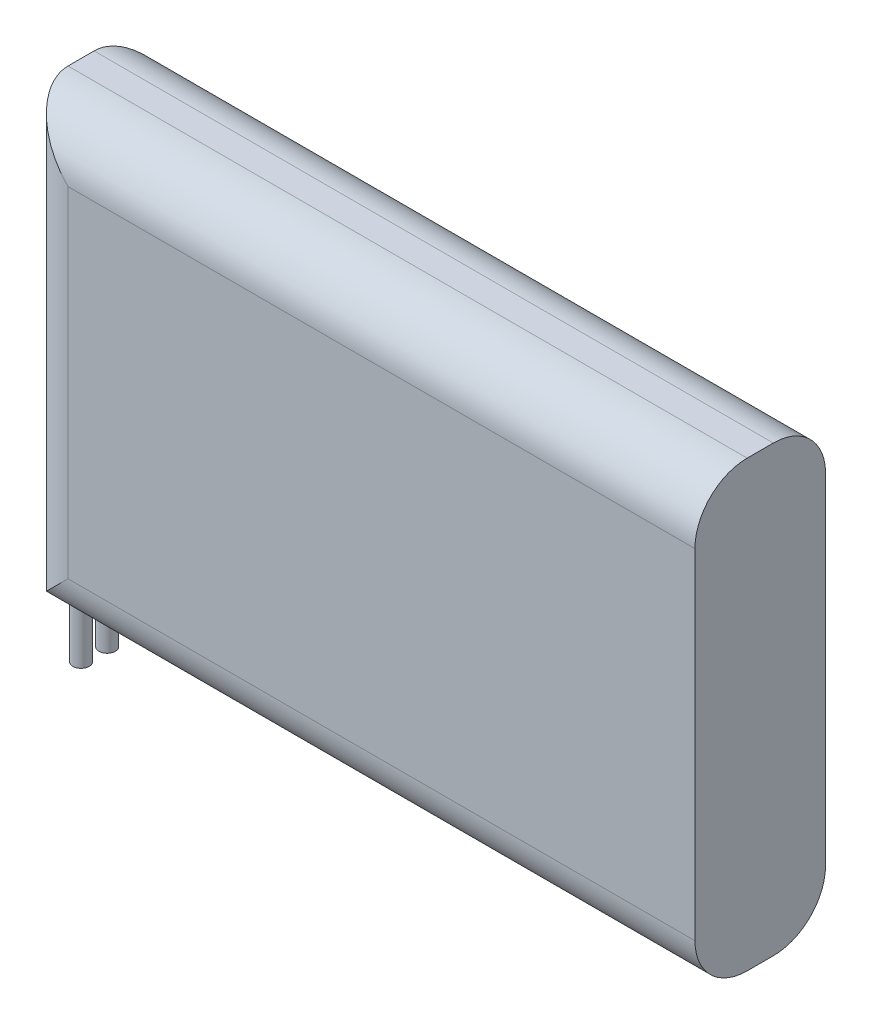
SolidWorks part; units mm, degrees
ref_plane "Front Plane" through (0, 0, 0) normal (0, 0, 1) x (1, 0, 0)
ref_plane "Top Plane" through (0, 0, 0) normal (0, 1, 0) x (1, 0, 0)
ref_plane "Right Plane" through (0, 0, 0) normal (1, 0, 0) x (0, 0, -1)
sketch "Sketch1" plane through (0, 0, 0) normal (0, 0, 1) x (1, 0, 0)
  line L1 (-26, -17) -> (26, -17)
  line L2 (-26, -17) -> (-26, 17)
  line L3 (-26, 17) -> (26, 17)
  line L4 (26, -17) -> (26, 17)
  line L5 (-26, -17) -> (26, 17) construction
  line L6 (-26, 17) -> (26, -17) construction
  point P0 (0, 0)
  dimension "D1" = 52
  dimension "D2" = 34
extrude "Boss-Extrude1" add sketch "Sketch1" along normal mid plane 10
sketch "Sketch2" plane through (0, -17, 0) normal (0, -1, 0) x (1, 0, 0)
  line L5 (-25, -1) -> (-25, 1) construction
  line L7 (-26, 5) -> (-26, -5) construction
  circle A0 centre (-25, 1) radius 0.625
  circle A1 centre (-25, -1) radius 0.625
  point P6 (-25, 1.1811)
  point P8 (-24.3944, -2.4812)
  point P9 (-26, 0)
  point P10 (-25, 0)
  point P11 (-25, -1.3036)
  point P12 (-25, 2.0469)
  dimension "D1" = 1.25
  dimension "D2" = 1
  dimension "D3" = 2
extrude "Boss-Extrude2" add sketch "Sketch2" along normal blind 5
fillet "Fillet1" radius 4 6 edges at (-26, 0, 5) (-26, 0, -5) (0, -17, -5) (0, -17, 5) (0, 17, -5) (0, 17, 5)
